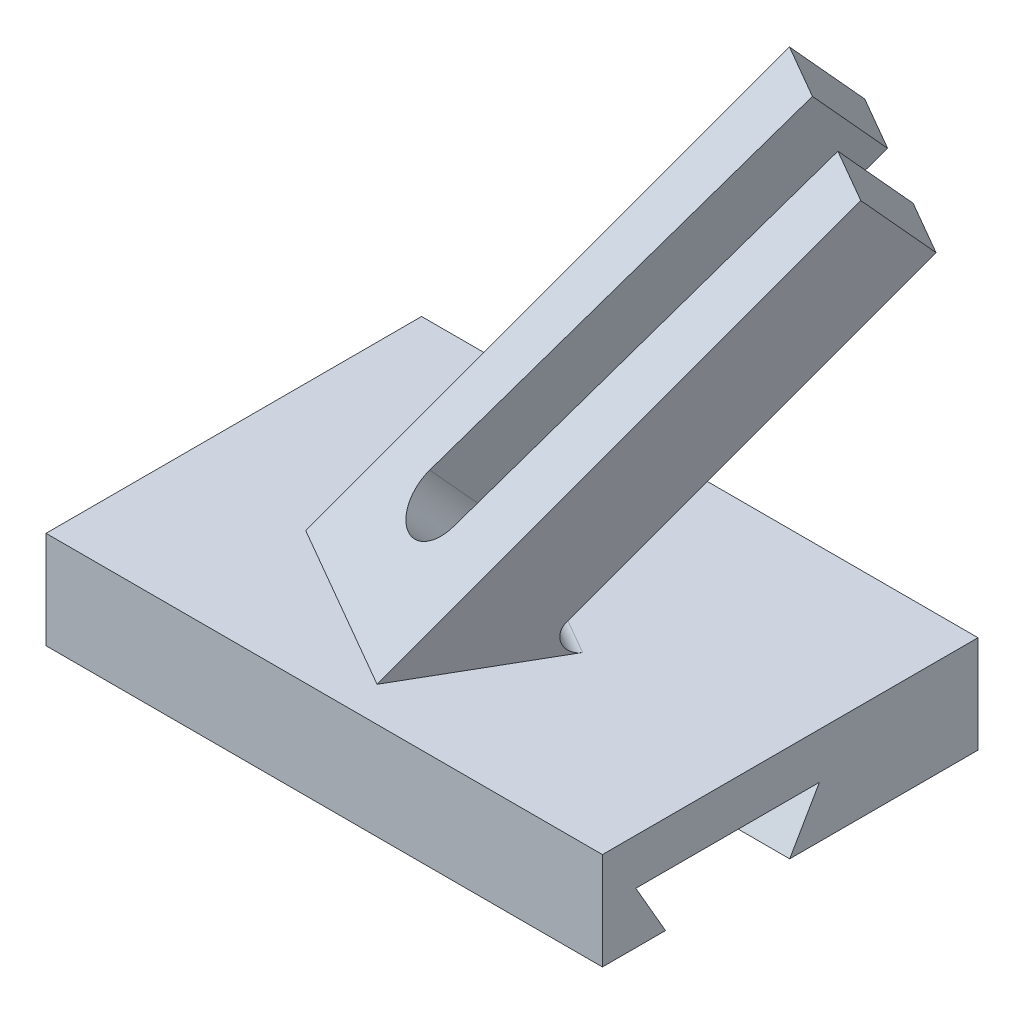
SolidWorks part; units mm, degrees
ref_plane "Front Plane" through (0, 0, 0) normal (0, 0, 1) x (1, 0, 0)
ref_plane "Top Plane" through (0, 0, 0) normal (0, 1, 0) x (1, 0, 0)
ref_plane "Right Plane" through (0, 0, 0) normal (1, 0, 0) x (0, 0, -1)
sketch "Croquis1" plane through (0, 0, 0) normal (0, 1, 0) x (1, 0, 0)
  line L1 (-100.0773, 67.5459) -> (1.5227, 67.5459)
  line L2 (-100.0773, 67.5459) -> (-100.0773, -1.0341)
  line L3 (-100.0773, -1.0341) -> (1.5227, -1.0341)
  line L4 (1.5227, 67.5459) -> (1.5227, -1.0341)
  dimension "D1" = 101.6
  dimension "D2" = 68.58
extrude "Saliente-Extruir1" add sketch "Croquis1" along normal blind 17.78
sketch "Croquis2" plane through (0, 17.78, 0) normal (0, 1, 0) x (1, 0, 0)
  line L0 (-45.9753, 5.3159) -> (-76.7711, 23.0959) construction
  line L1 (-100.0773, -1.0341) -> (1.5227, -1.0341) construction
  line L2 (1.5227, -1.0341) -> (1.5227, 67.5459) construction
  point P2 (0, 0)
  dimension "D1" = 35.56
  dimension "D2" = 6.35
  dimension "D3" = 47.498
  dimension "D4" = 30
ref_plane "Plano1" through (-9.041, 18.082, 15.6594) normal (-0.3536, 0.7071, 0.6124) x (-0.866, 0, -0.5)
sketch "Croquis3" plane through (-9.041, 18.082, 15.6594) normal (-0.3536, 0.7071, 0.6124) x (-0.866, 0, -0.5)
  line L0 (42.4737, 0.427) -> (78.0337, 0.427)
  line L1 (78.0337, 0.427) -> (78.0337, -91.013)
  line L2 (78.0337, -91.013) -> (42.4737, -91.013)
  line L3 (42.4737, -91.013) -> (42.4737, 0.427)
  dimension "D1" = 91.44
extrude "Saliente-Extruir2" add sketch "Croquis3" against normal blind 14.224
sketch "Croquis4" plane through (-9.041, 18.082, 15.6594) normal (-0.3536, 0.7071, 0.6124) x (0.9354, 0.2673, 0.2315)
  line L0 (-21.3844, 107.0354) -> (-49.8773, 40.9954) construction
  line L1 (-4.9233, 100.3152) -> (-37.8455, 113.7556) construction
  line L2 (-27.2634, 109.4355) -> (-15.5055, 104.6353)
  line L3 (-15.5055, 104.6353) -> (-44.0553, 38.4633)
  line L4 (-27.1642, 109.6654) -> (-55.714, 43.4934)
  arc A0 (-44.0553, 38.4633) -> (-55.714, 43.4934) centre (-49.8846, 40.9784) cw
  point P7 (-21.3844, 107.0354)
  point P10 (0, 0)
  point P11 (0, 0)
  dimension "D1" = 66.04
  dimension "D2" = 12.7
extrude "Cortar-Extruir2" cut sketch "Croquis4" against normal blind 14.224
fillet "Redondeo5" radius 3.048 2 edges at (-61.1506, 17.78, -37.3051) (-42.7088, 17.78, -26.6577)
sketch "Croquis5" plane through (1.5227, 0, 0) normal (1, 0, 0) x (0, 0, -1)
  line L0 (-1.0341, 17.78) -> (-1.0341, 0) construction
  line L1 (-1.0341, 0) -> (67.5459, 0) construction
  line L2 (5.0619, 9.398) -> (38.5899, 9.398)
  line L3 (5.0619, 9.398) -> (10.4878, 0)
  line L4 (38.5899, 9.398) -> (33.164, 0)
  line L5 (33.164, 0) -> (10.4878, 0)
  point P0 (21.8259, 9.398)
  point P8 (21.8259, 9.398)
  dimension "D1" = 22.86
  dimension "D2" = 9.398
  dimension "D3" = 33.528
  dimension "D4" = 60
  dimension "D5" = 60
extrude "Cortar-Extruir3" cut sketch "Croquis5" against normal through all
